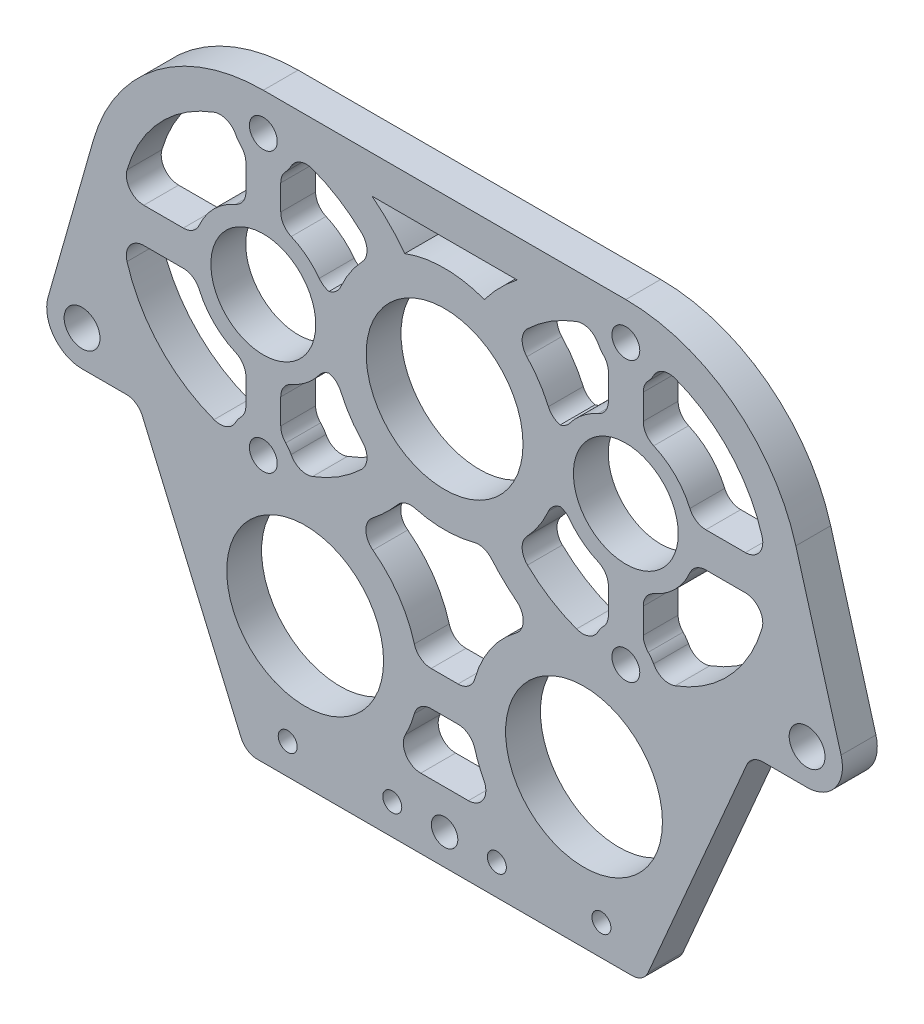
SolidWorks part; units mm, degrees
material "6061 Alloy"
ref_plane "Front Plane" through (0, 0, 0) normal (0, 0, 1) x (1, 0, 0)
ref_plane "Top Plane" through (0, 0, 0) normal (0, 1, 0) x (1, 0, 0)
ref_plane "Right Plane" through (0, 0, 0) normal (1, 0, 0) x (0, 0, -1)
sketch "Sketch1" plane through (0, 0, 0) normal (0, 0, 1) x (1, 0, 0)
  line L0 (-88.7296, -57.0475) -> (-96.9696, -85.9369)
  line L1 (-70.0805, -62.7064) -> (-83.4191, -62.7064)
  line L2 (-60.9326, -45.2333) -> (-60.9326, -53.5585)
  line L3 (-60.9326, -86.5295) -> (-60.9326, -78.2044)
  line L4 (-54.5826, -45.2333) -> (-54.5826, -53.5585)
  line L5 (-46.7298, -59.5314) -> (-44.3739, -59.5314)
  line L6 (-54.5826, -86.5295) -> (-54.5826, -78.2044)
  line L7 (-70.0805, -69.0564) -> (-83.4191, -69.0564)
  line L8 (-60.9774, -139.773) -> (-79.8712, -95.883)
  line L9 (-46.7298, -72.2314) -> (-44.3739, -72.2314)
  line L10 (-24.7376, -4.929) -> (-24.7376, -7.3556)
  line L12 (41.3024, -94.1419) -> (33.2559, -94.1419)
  line L13 (-29.7458, -109.6105) -> (-19.7294, -109.6105)
  line L14 (-14.2297, -127.073) -> (-35.2455, -127.073)
  line L15 (-29.7458, -115.9605) -> (-19.7294, -115.9605)
  line L16 (-57.7576, -33.6742) -> (8.2824, -33.6742)
  line L17 (-11.5202, -40.4814) -> (-37.955, -40.4814)
  line L19 (-2.7454, -72.2314) -> (-5.1013, -72.2314)
  line L20 (11.5022, -139.773) -> (30.396, -95.883)
  line L21 (20.6054, -69.0564) -> (33.9439, -69.0564)
  line L22 (5.1074, -86.5295) -> (5.1074, -78.2044)
  line L23 (-2.7454, -59.5314) -> (-5.1013, -59.5314)
  line L24 (5.1074, -45.2333) -> (5.1074, -53.5585)
  line L25 (11.4574, -86.5295) -> (11.4574, -78.2044)
  line L26 (11.4574, -45.2333) -> (11.4574, -53.5585)
  line L27 (20.6054, -62.7064) -> (33.9439, -62.7064)
  line L28 (39.2544, -57.0475) -> (47.4944, -85.9369)
  line L29 (-90.7776, -94.1419) -> (-82.7311, -94.1419)
  line L31 (-60.9774, -139.773) -> (11.5022, -139.773)
  circle A0 centre (-57.7576, -65.8814) radius 9.5504
  circle A1 centre (-57.7576, -40.4814) radius 2.54
  arc A2 (-41.8493, -93.8855) -> (-31.9896, -85.2028) centre (-57.7576, -65.8814) ccw
  circle A3 centre (-57.7576, -91.2814) radius 2.54
  circle A4 centre (-90.7776, -87.703) radius 3.2639
  arc A5 (-52.0455, -91.0998) -> (-54.5826, -86.5295) centre (-57.7576, -91.2814) ccw
  arc A6 (-52.0455, -91.0998) -> (-37.5727, -82.042) centre (-57.7576, -65.8814) ccw
  arc A7 (-52.0455, -40.663) -> (-54.5826, -45.2333) centre (-57.7576, -40.4814) cw
  arc A8 (-60.9326, -45.2333) -> (-63.4697, -40.663) centre (-57.7576, -40.4814) cw
  arc A9 (-54.5826, -78.2044) -> (-46.7298, -72.2314) centre (-57.7576, -65.8814) ccw
  arc A10 (-60.9326, -86.5295) -> (-63.4697, -91.0998) centre (-57.7576, -91.2814) ccw
  arc A11 (-83.4191, -69.0564) -> (-63.4697, -91.0998) centre (-57.7576, -65.8814) ccw
  arc A12 (-60.9326, -53.5585) -> (-70.0805, -62.7064) centre (-57.7576, -65.8814) ccw
  circle A13 centre (-50.1376, -112.7855) radius 14.2875
  arc A14 (-70.0805, -69.0564) -> (-60.9326, -78.2044) centre (-57.7576, -65.8814) ccw
  arc A15 (-46.7298, -59.5314) -> (-54.5826, -53.5585) centre (-57.7576, -65.8814) ccw
  arc A16 (-63.4697, -40.663) -> (-83.4191, -62.7064) centre (-57.7576, -65.8814) ccw
  arc A17 (-31.9896, -85.2028) -> (-17.4856, -85.2028) centre (-24.7376, -65.8814) ccw
  circle A20 centre (-24.7376, -65.8814) radius 14.2875
  arc A21 (-37.5727, -49.7208) -> (-44.3739, -59.5314) centre (-24.7376, -65.8814) ccw
  arc A22 (-37.5727, -49.7208) -> (-52.0455, -40.663) centre (-57.7576, -65.8814) ccw
  arc A23 (-44.3739, -72.2314) -> (-37.5727, -82.042) centre (-24.7376, -65.8814) ccw
  arc A24 (-31.9896, -46.5601) -> (-37.955, -40.4814) centre (-57.7576, -65.8814) ccw
  arc A25 (-17.4856, -46.5601) -> (-31.9896, -46.5601) centre (-24.7376, -65.8814) ccw
  arc A26 (-29.7458, -109.6105) -> (-41.8493, -93.8855) centre (-50.1376, -112.7855) ccw
  arc A27 (-35.2455, -127.073) -> (-29.7458, -115.9605) centre (-50.1376, -112.7855) ccw
  arc A28 (-57.7576, -33.6742) -> (-88.6501, -56.7733) centre (-57.7576, -65.8814) ccw
  arc A29 (39.1749, -56.7733) -> (39.2544, -57.0475) centre (8.2824, -65.8814) cw
  arc A30 (30.396, -95.883) -> (33.2559, -94.1419) centre (33.2559, -97.3614) cw
  circle A31 centre (-15.2126, -134.185) radius 1.7272
  circle A32 centre (3.8374, -134.185) radius 1.7272
  arc A33 (47.4944, -85.9369) -> (41.3024, -94.1419) centre (41.3024, -87.703) cw
  arc A34 (8.2824, -33.6742) -> (39.1749, -56.7733) centre (8.2824, -65.8814) cw
  arc A35 (-14.2297, -127.073) -> (-19.7294, -115.9605) centre (0.6624, -112.7855) cw
  arc A36 (-19.7294, -109.6105) -> (-7.6259, -93.8855) centre (0.6624, -112.7855) cw
  arc A37 (-17.4856, -46.5601) -> (-11.5202, -40.4814) centre (8.2824, -65.8814) cw
  arc A38 (-5.1013, -72.2314) -> (-11.9025, -82.042) centre (-24.7376, -65.8814) cw
  arc A39 (-11.9025, -49.7208) -> (2.5703, -40.663) centre (8.2824, -65.8814) cw
  arc A40 (-11.9025, -49.7208) -> (-5.1013, -59.5314) centre (-24.7376, -65.8814) cw
  arc A42 (13.9945, -40.663) -> (33.9439, -62.7064) centre (8.2824, -65.8814) cw
  arc A43 (-2.7454, -59.5314) -> (5.1074, -53.5585) centre (8.2824, -65.8814) cw
  arc A44 (20.6054, -69.0564) -> (11.4574, -78.2044) centre (8.2824, -65.8814) cw
  circle A45 centre (0.6624, -112.7855) radius 14.2875
  arc A46 (11.4574, -53.5585) -> (20.6054, -62.7064) centre (8.2824, -65.8814) cw
  arc A47 (33.9439, -69.0564) -> (13.9945, -91.0998) centre (8.2824, -65.8814) cw
  arc A48 (11.4574, -86.5295) -> (13.9945, -91.0998) centre (8.2824, -91.2814) cw
  arc A49 (5.1074, -78.2044) -> (-2.7454, -72.2314) centre (8.2824, -65.8814) cw
  arc A50 (-96.9696, -85.9369) -> (-90.7776, -94.1419) centre (-90.7776, -87.703) ccw
  arc A51 (11.4574, -45.2333) -> (13.9945, -40.663) centre (8.2824, -40.4814) ccw
  arc A52 (2.5703, -40.663) -> (5.1074, -45.2333) centre (8.2824, -40.4814) ccw
  arc A53 (2.5703, -91.0998) -> (-11.9025, -82.042) centre (8.2824, -65.8814) cw
  arc A54 (2.5703, -91.0998) -> (5.1074, -86.5295) centre (8.2824, -91.2814) cw
  circle A55 centre (-53.3126, -134.185) radius 1.7272
  circle A56 centre (-24.7376, -134.185) radius 2.413
  circle A57 centre (-34.2626, -134.185) radius 1.7272
  circle A58 centre (41.3024, -87.703) radius 3.2639
  circle A59 centre (8.2824, -91.2814) radius 2.54
  arc A60 (-79.8712, -95.883) -> (-82.7311, -94.1419) centre (-82.7311, -97.3614) ccw
  arc A61 (-7.6259, -93.8855) -> (-17.4856, -85.2028) centre (8.2824, -65.8814) cw
  circle A62 centre (8.2824, -40.4814) radius 2.54
  circle A63 centre (8.2824, -65.8814) radius 9.5504
  arc A65 (-88.6501, -56.7733) -> (-88.7296, -57.0475) centre (-57.7576, -65.8814) ccw
  point P3 (-24.7376, -65.8814)
  point P32 (-24.7376, -33.6742)
  point P51 (-24.7376, -115.9605)
  point P64 (-24.7376, -127.073)
  point P109 (-60.9774, -139.773)
  point P112 (-24.7376, -109.6105)
  point P118 (-45.5518, -59.5314)
  point P120 (-24.7376, -139.773)
  point P121 (-24.7376, -40.4814)
  dimension "D1" = 28.575
  dimension "D2" = 19.1008
  dimension "D4" = 33.02
  dimension "D8" = 25.4
  dimension "D9" = 12.7254
  dimension "D10" = 25.8572
  dimension "D11" = 25.8572
  dimension "D12" = 32.2072
  dimension "D13" = 25.4
  dimension "D14" = 46.9041
  dimension "D15" = 28.575
  dimension "D17" = 25.4
  dimension "D18" = 5.08
  dimension "D23" = 25.4
  dimension "D27" = 3.175
  dimension "D7" = 3.175
  dimension "D28" = 6.35
  dimension "D29" = 3.175
  dimension "D30" = 12.7
  dimension "D5" = 33.02
  dimension "D16" = 33.02
  dimension "D24" = 6.35
  dimension "D25" = 3.175
  dimension "D26" = 6.35
  dimension "D40" = 3.2194
  dimension "D41" = 9.6584
  dimension "D42" = 28.575
  dimension "D6" = 5.08
  dimension "D19" = 3.175
  dimension "D20" = 20.6375
  dimension "D21" = 20.6375
  dimension "D22" = 6.35
  dimension "D32" = 66.04
  dimension "D34" = 6.5278
  dimension "D35" = 3.175
  dimension "D47" = 10.5079
  dimension "D52" = 3.4544
  dimension "D53" = 3.4544
  dimension "D56" = 2.413
  dimension "D31" = 6.35
  dimension "D33" = 21.8216
  dimension "D38" = 8.0465
  dimension "D43" = 73.8916
  dimension "D48" = 6.35
  dimension "D49" = 3.175
  dimension "D50" = 9.525
  dimension "D51" = 5.588
  dimension "D54" = 5.588
  dimension "D55" = 5.588
  dimension "D57" = 36.2398
  dimension "D58" = 47.784
extrude "Boss-Extrude1" add sketch "Sketch1" along normal blind 6.35 contours A0 region at (-24.7376, -84.6658, 0)
fillet "Fillet1" radius 3.175 44 edges at (-83.4191, -62.7064, 3.175) (-63.4697, -40.663, 3.175) (-60.9326, -45.2333, 3.175) (-60.9326, -53.5585, 3.175) (-70.0805, -62.7064, 3.175) (-5.1013, -59.5314, 3.175) (-2.7454, -59.5314, 3.175) (-2.7454, -72.2314, 3.175) (-5.1013, -72.2314, 3.175) (-11.9025, -82.042, 3.175) (5.1074, -78.2044, 3.175) (2.5703, -91.0998, 3.175) (5.1074, -86.5295, 3.175) (13.9945, -91.0998, 3.175) (11.4574, -86.5295, 3.175) (11.4574, -78.2044, 3.175) (20.6054, -69.0564, 3.175) (33.9439, -69.0564, 3.175) (33.9439, -62.7064, 3.175) (11.4574, -53.5585, 3.175) (20.6054, -62.7064, 3.175) (13.9945, -40.663, 3.175) (11.4574, -45.2333, 3.175) (5.1074, -53.5585, 3.175) (5.1074, -45.2333, 3.175) (2.5703, -40.663, 3.175) (-11.9025, -49.7208, 3.175) (-44.3739, -59.5314, 3.175) (-46.7298, -59.5314, 3.175) (-46.7298, -72.2314, 3.175) (-44.3739, -72.2314, 3.175) (-37.5727, -82.042, 3.175) (-52.0455, -91.0998, 3.175) (-54.5826, -86.5295, 3.175) (-54.5826, -78.2044, 3.175) (-63.4697, -91.0998, 3.175) (-60.9326, -86.5295, 3.175) (-60.9326, -78.2044, 3.175) (-70.0805, -69.0564, 3.175) (-83.4191, -69.0564, 3.175) (-37.5727, -49.7208, 3.175) (-54.5826, -53.5585, 3.175) (-54.5826, -45.2333, 3.175) (-52.0455, -40.663, 3.175)
fillet "Fillet2" radius 3.175 10 edges at (-14.2297, -127.073, 3.175) (-35.2455, -127.073, 3.175) (-19.7294, -115.9605, 3.175) (-29.7458, -115.9605, 3.175) (-19.7294, -109.6105, 3.175) (-29.7458, -109.6105, 3.175) (-41.8493, -93.8855, 3.175) (-7.6259, -93.8855, 3.175) (-17.4856, -85.2028, 3.175) (-31.9896, -85.2028, 3.175)
fillet "Fillet3" radius 3.175 2 edges at (11.5022, -139.773, 3.175) (-60.9774, -139.773, 3.175)
